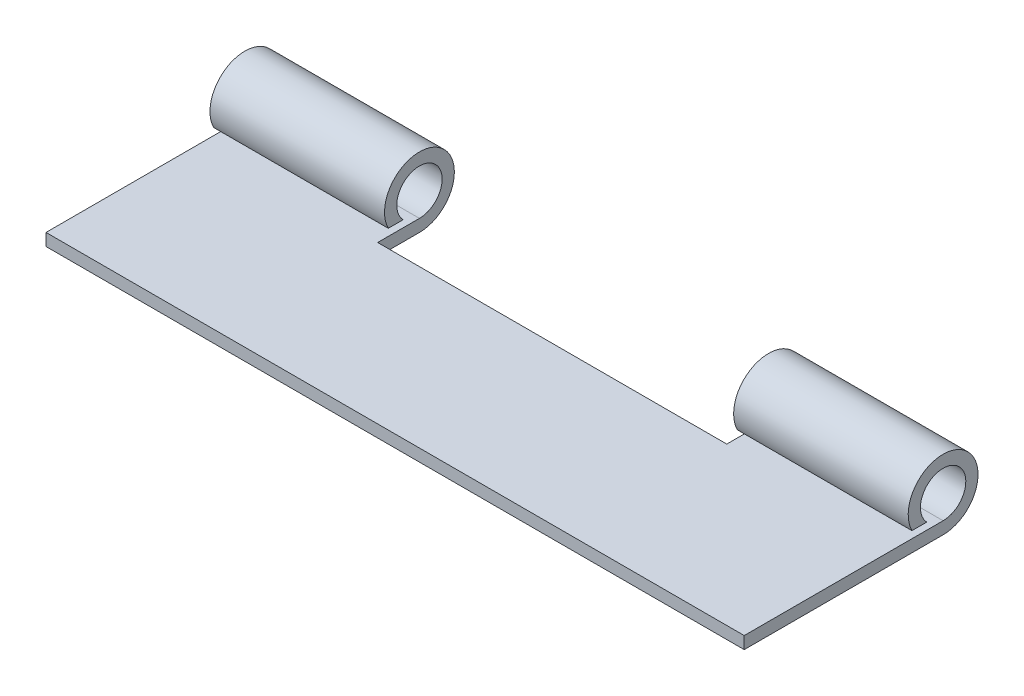
SolidWorks part; units mm, degrees
material "AISI 1020 Steel, Cold Rolled"
ref_plane "Front Plane" through (0, 0, 0) normal (0, 0, 1) x (1, 0, 0)
ref_plane "Top Plane" through (0, 0, 0) normal (0, 1, 0) x (1, 0, 0)
ref_plane "Right Plane" through (0, 0, 0) normal (1, 0, 0) x (0, 0, -1)
sketch "Sketch1" plane through (0, 0, 0) normal (0, 1, 0) x (1, 0, 0)
  line L1 (0, 0) -> (50.8, 0)
  line L2 (0, 0) -> (0, 15.875)
  line L3 (0, 15.875) -> (50.8, 15.875)
  line L4 (50.8, 0) -> (50.8, 15.875)
  dimension "D1" = 15.875
  dimension "D2" = 50.8
extrude "Boss-Extrude1" add sketch "Sketch1" along normal blind 0.889
ref_plane "Plane1" through (38.1, 0, 0) normal (1, 0, 0) x (0, 0, -1)
sketch "Sketch2" plane through (38.1, 0, 0) normal (1, 0, 0) x (0, 0, -1)
  line L0 (0, 0.889) -> (15.875, 0.889) construction
  line L1 (0, 0) -> (15.875, 0) construction
  line L2 (0, 0.889) -> (15.875, 0.889)
  line L3 (0, 0) -> (15.875, 0)
  line L4 (16.4171, 0.7337) -> (17.3285, -0.1092)
  line L5 (15.875, 0) -> (16.9772, -1.3136)
  line L6 (15.875, 0) -> (15.875, 0.889)
  line L7 (15.875, 0.889) -> (17.8021, -0.8931)
  arc A0 (16.9772, -1.3136) -> (16.4171, 0.7337) centre (18.923, 0.3191) ccw
  arc A1 (17.8021, -0.8931) -> (17.3285, -0.1092) centre (18.923, 0.3191) ccw
  dimension "D1" = 5.08
  dimension "D3" = 0.889
  dimension "D2" = 3.048
  dimension "D4" = 0.254
  dimension "D5" = 130
extrude "Boss-Extrude2" [suppressed] add sketch "Sketch2" against normal blind 25.4 contours A0 A1 | A0 L7 L6 L5
sketch "Sketch4" plane through (38.1, 0, 0) normal (1, 0, 0) x (0, 0, -1)
  line L0 (0, 0) -> (15.875, 0) construction
  line L1 (15.875, 0.889) -> (18.9151, 0.889)
  line L2 (15.875, 0.889) -> (15.875, 0)
  line L3 (15.875, 0) -> (18.9151, 0)
  line L5 (16.6468, 1.397) -> (17.7237, 1.397)
  arc A0 (18.9151, 0.889) -> (17.7237, 1.397) centre (18.9151, 2.54) ccw
  arc A1 (18.9151, 0) -> (16.6468, 1.397) centre (18.9151, 2.54) ccw
  point P1 (0, 0)
  dimension "D1" = 5.08
  dimension "D2" = 3.0401
  dimension "D3" = 0.508
sketch "Sketch3" plane through (50.8, 0, 0) normal (1, 0, 0) x (0, 0, -1)
  line L1 (4.445, 6.3403) -> (-3.175, 6.3403)
  line L2 (4.445, 6.3403) -> (4.445, -6.3597)
  line L3 (4.445, -6.3597) -> (-3.175, -6.3597)
  line L4 (-3.175, 6.3403) -> (-3.175, -6.3597)
  line L5 (15.875, 0.889) -> (15.875, 0) construction
  dimension "D1" = 11.43
  dimension "D2" = 7.62
  dimension "D3" = 12.7
  dimension "D4" = 6.3597
extrude "Cut-Extrude1" cut sketch "Sketch3" against normal through all
extrude "Boss-Extrude6" add sketch "Sketch4" along normal up to surface (12.7 mm away) contours A0 L5 A1 L3 L2 L1 up to face at (50.8, 0.4445, -10.16)
extrude "Boss-Extrude7" add sketch "Sketch4<4>" against normal up to surface (38.1 mm away) from offset 25.4 up to face at (0, 0.4445, -10.16) offset against normal yes
sketch "Sketch4<4>" plane through (38.1, 0, 0) normal (1, 0, 0) x (0, 0, -1) same geometry as "Sketch4"
